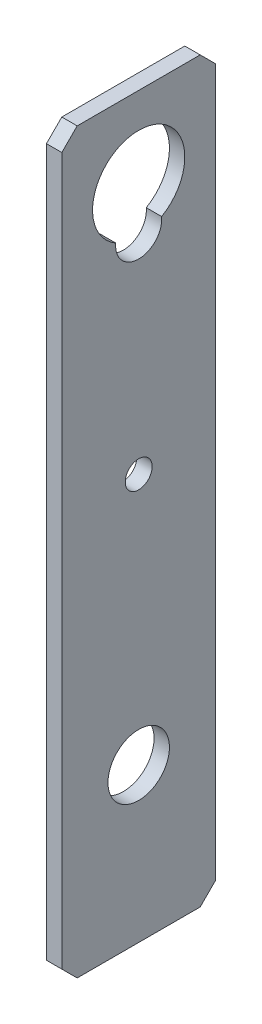
SolidWorks part; units mm, degrees
ref_plane "Front Plane" through (0, 0, 0) normal (0, 0, 1) x (1, 0, 0)
ref_plane "Top Plane" through (0, 0, 0) normal (0, 1, 0) x (1, 0, 0)
ref_plane "Right Plane" through (0, 0, 0) normal (1, 0, 0) x (0, 0, -1)
sketch "Sketch1" plane through (0, 0, 0) normal (1, 0, 0) x (0, 0, -1)
  line L1 (-10, -48) -> (10, -48)
  line L2 (-10, -48) -> (-10, 48)
  line L3 (-10, 48) -> (10, 48)
  line L4 (10, -48) -> (10, 48)
  line L5 (-10, -48) -> (10, 48) construction
  line L6 (-10, 48) -> (10, -48) construction
  point P0 (0, 0)
  dimension "D1" = 96
  dimension "D2" = 20
extrude "Boss-Extrude2" add sketch "Sketch1" along normal blind 2
sketch "Sketch3" plane through (2, 0, 0) normal (1, 0, 0) x (0, 0, -1)
  line L0 (-10, -48) -> (10, -48) construction
  line L1 (10, 48) -> (-10, 48) construction
  circle A0 centre (0, 4.75) radius 1.75
  arc A1 (2.9854, 32.2955) -> (-2.9854, 32.2955) centre (0, 37.5) ccw
  circle A2 centre (0, -28) radius 4
  arc A3 (-2.9854, 32.2955) -> (2.9854, 32.2955) centre (0, 32) ccw
  dimension "D1" = 8
  dimension "D2" = 3.5
  dimension "D3" = 12
  dimension "D4" = 32.75
  dimension "D7" = 5.5
  dimension "D8" = 6
  dimension "D5" = 20
  dimension "D6" = 10.5
extrude "Cut-Extrude1" cut sketch "Sketch3" against normal through all
chamfer "Chamfer1" distance 2 angle 45 4 edges at (1, -48, 10) (1, -48, -10) (1, 48, -10) (1, 48, 10)
